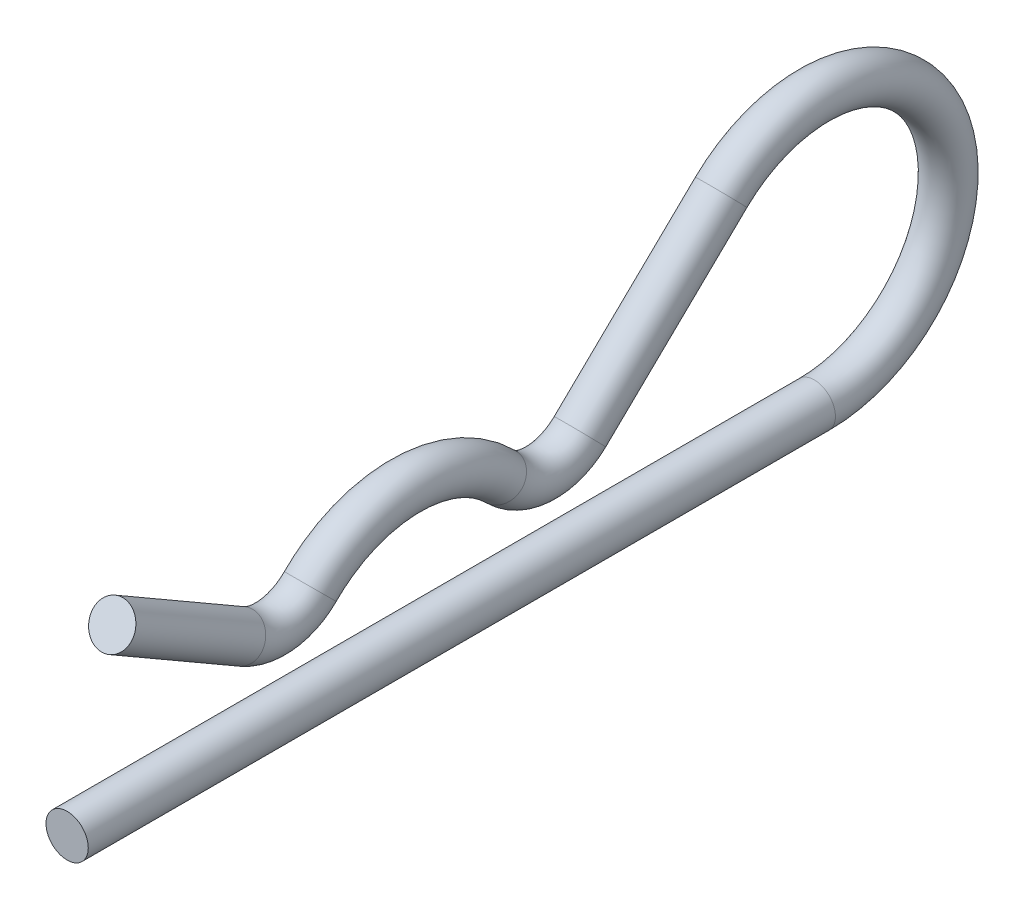
SolidWorks part; units mm, degrees
material "Plain Carbon Steel"
ref_plane "Front" through (0, 0, 0) normal (0, 0, 1) x (1, 0, 0)
ref_plane "Top" through (0, 0, 0) normal (0, 1, 0) x (1, 0, 0)
ref_plane "Right" through (0, 0, 0) normal (1, 0, 0) x (0, 0, -1)
sketch "Sketch1" plane through (0, 0, 0) normal (0, 0, 1) x (1, 0, 0)
  circle A0 centre (0, 0) radius 0.5953
sketch "Sketch2" plane through (0, 0, 0) normal (1, 0, 0) x (0, 0, -1)
  line L0 (0, 0) -> (21.0344, 0)
  line L1 (5.7183, 3.7703) -> (13.3317, 3.7703) construction
  line L2 (25.4, 0) -> (25.4, 3.7703) construction
  line L3 (25.4, 3.7703) -> (24.8047, 3.7703) construction
  line L5 (25.4, 0) -> (0, 0) construction
  line L6 (4.9246, 2.3955) -> (1.27, 4.5055)
  line L7 (9.525, 3.7703) -> (9.525, 0) construction
  line L13 (18.4118, 6.4791) -> (14.4359, 2.6298)
  circle A0 centre (21.0344, 3.7703) radius 3.175 construction
  arc A1 (12.2038, 2.6532) -> (6.8462, 2.6532) centre (9.525, 0) ccw
  arc A6 (6.8462, 2.6532) -> (4.9246, 2.3955) centre (5.7183, 3.7703) cw
  arc A8 (14.4359, 2.6298) -> (12.2038, 2.6532) centre (13.3317, 3.7703) cw
  arc A9 (21.0344, 0) -> (18.4118, 6.4791) centre (21.0344, 3.7703) ccw
  dimension "D1" = 1.5875
  dimension "D2" = 9.525
  dimension "D5" = 1.27
  dimension "D9" = 30
  dimension "D11" = 0.5953
  dimension "D3" = 0.5953
sweep "Sweep1" add profiles "Sketch1" path "Sketch2"
sketch "Sketch3" plane through (0, 0, 0) normal (1, 0, 0) x (0, 0, -1)
  line L0 (-2.8969, 0) -> (27.788, 0) construction
  line L1 (0, -3.3157) -> (0, 8.0575) construction
equation "\"D11@Sketch2\" = \"WireOD@Sketch1\"/2"
equation "\"D1@Sketch2\" = \"EyeID@Sketch2\"/4"
equation "\"D3@Sketch2\" = \"D11@Sketch2\""
equation "\"D2@Sketch2\" = (\"Length@Sketch2\"-\"EyeID@Sketch2\")/2"
equation "\"D5@Sketch2\" = \"Length@Sketch2\"*.05"
